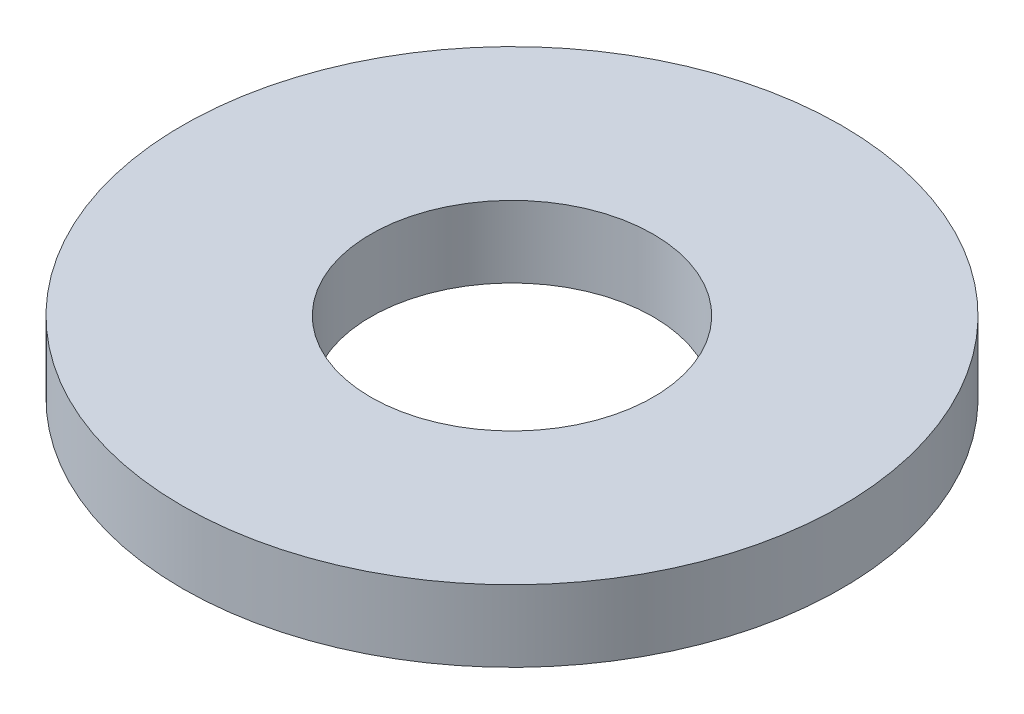
SolidWorks part; units mm, degrees
ref_plane "Front Plane" through (0, 0, 0) normal (0, 0, 1) x (1, 0, 0)
ref_plane "Top Plane" through (0, 0, 0) normal (0, 1, 0) x (1, 0, 0)
ref_plane "Right Plane" through (0, 0, 0) normal (1, 0, 0) x (0, 0, -1)
sketch "Sketch1" plane through (0, 0, 0) normal (0, 1, 0) x (1, 0, 0)
  circle A0 centre (0, 0) radius 87.5
  dimension "FLANGE_OD" = 175
extrude "Boss-Extrude1" add sketch "Sketch1" along normal blind 19
sketch "Sketch2" plane through (0, 0, 0) normal (0, 1, 0) x (1, 0, 0)
  circle A0 centre (0, 0) radius 37.5
  dimension "BORE_D" = 75
extrude "Cut-Extrude1" cut sketch "Sketch2" along normal through all
sketch "Sketch3" plane through (0, 19, 0) normal (0, 1, 0) x (1, 0, 0)
  circle A0 centre (0, 0) radius 21.6507 construction
  circle A1 centre (-21.6507, 0) radius 4.697
  dimension "BOLT_D" = 9.394
  dimension "BOLT_PCD" = 43.3014
extrude "Cut-Extrude2" cut sketch "Sketch3" against normal blind 14.9139 rebuild error yes
pattern_circular "CirPattern1" count 3 over 360 rebuild error yes
